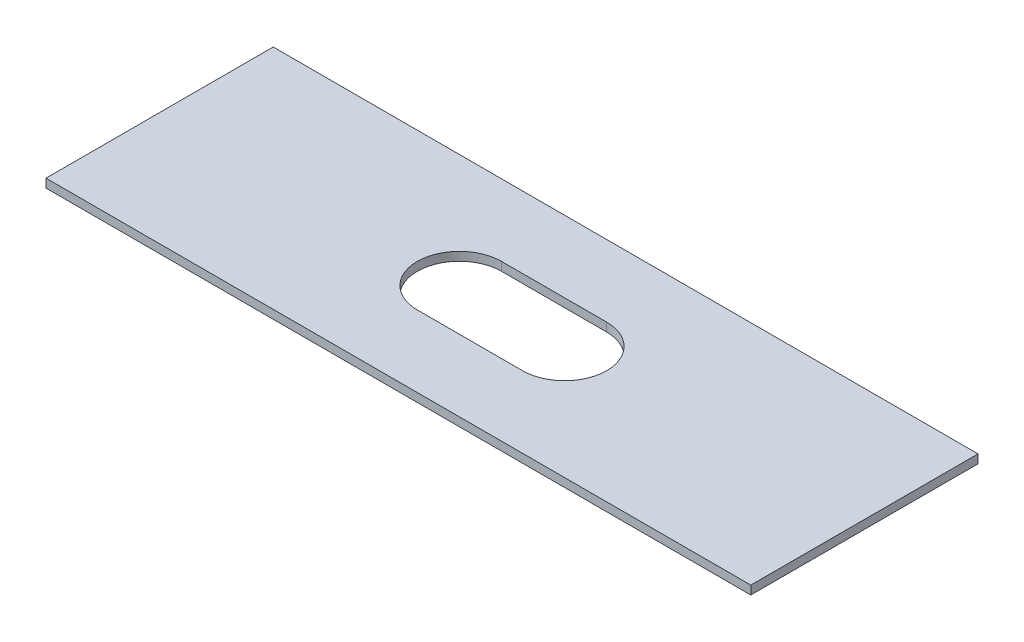
SolidWorks part; units mm, degrees
ref_plane "Front Plane" through (0, 0, 0) normal (0, 0, 1) x (1, 0, 0)
ref_plane "Top Plane" through (0, 0, 0) normal (0, 1, 0) x (1, 0, 0)
ref_plane "Right Plane" through (0, 0, 0) normal (1, 0, 0) x (0, 0, -1)
sketch "Sketch1" plane through (0, 0, 0) normal (0, 1, 0) x (1, 0, 0)
  line L1 (-167.5, 54) -> (167.5, 54)
  line L2 (-167.5, 54) -> (-167.5, -54)
  line L3 (-167.5, -54) -> (167.5, -54)
  line L4 (167.5, 54) -> (167.5, -54)
  line L5 (-167.5, 54) -> (167.5, -54) construction
  line L6 (-167.5, -54) -> (167.5, 54) construction
  point P0 (0, 0)
  dimension "D1" = 335
  dimension "D2" = 108
extrude "Boss-Extrude2" add sketch "Sketch1" along normal blind 4.0952
sketch "Sketch3" plane through (0, 4.0952, 0) normal (0, 1, 0) x (1, 0, 0)
  line L0 (-25, 0) -> (25, 0) construction
  line L1 (-25, 20) -> (25, 20)
  line L2 (-25, -20) -> (25, -20)
  arc A0 (-25, 20) -> (-25, -20) centre (-25, 0) ccw
  arc A1 (25, -20) -> (25, 20) centre (25, 0) ccw
  point P3 (0, 0)
  dimension "D2" = 20
  dimension "D1" = 50
extrude "Cut-Extrude1" cut sketch "Sketch3" against normal blind 5 contours L2 A1 L1 A0
